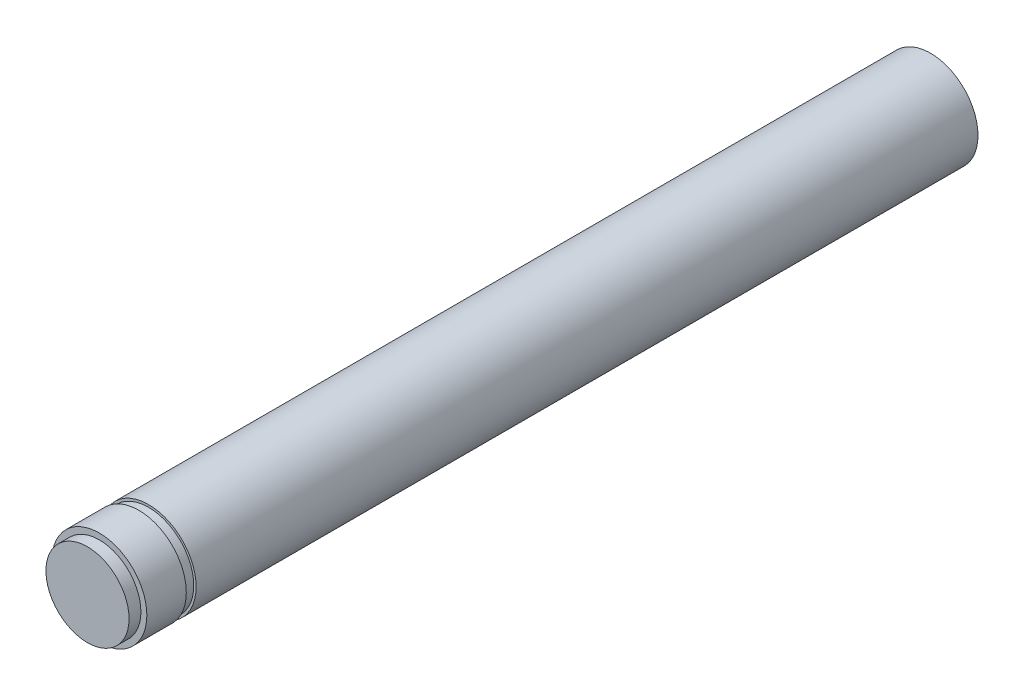
SolidWorks part; units mm, degrees
ref_plane "Front Plane" through (0, 0, 0) normal (0, 0, 1) x (1, 0, 0)
ref_plane "Top Plane" through (0, 0, 0) normal (0, 1, 0) x (1, 0, 0)
ref_plane "Right Plane" through (0, 0, 0) normal (1, 0, 0) x (0, 0, -1)
ref_axis "Z" through (0, 0, -3.55) along (0, 0, 1)
sketch "Sketch2" plane through (0, 0, 0) normal (0, 1, 0) x (1, 0, 0)
  line L0 (0, 0) -> (0, -70)
  line L1 (0, 0) -> (4, 0)
  line L2 (0, -25.9144) -> (0, 43.7641) construction
  line L3 (4, 0) -> (4, -65.8508)
  line L4 (4, -70) -> (0, -70) construction
  line L5 (3.5, -70) -> (3.5, -71)
  line L6 (3.5, -71) -> (0, -71)
  line L7 (0, -71) -> (0, -70)
  line L8 (3.5, -70) -> (4, -70)
  line L9 (4, -66.6762) -> (3.8, -66.6762)
  line L10 (3.8, -66.6762) -> (3.8, -65.8508)
  line L11 (3.8, -65.8508) -> (4, -65.8508)
  line L12 (4, -66.6762) -> (4, -70)
  line L13 (4, -65.8508) -> (4, -66.6762) construction
  point P9 (3.5596, -58.9398)
  point P15 (1.8672, -60.8973)
  point P16 (3.8, -68.2732)
  dimension "D1" = 70
  dimension "D2" = 4
  dimension "D3" = 1
  dimension "D4" = 7
  dimension "D5" = 0.8254
  dimension "D6" = 7.6
  dimension "D7" = 65.8508
revolve "Revolve1" add sketch "Sketch2" angle 360 about L2
